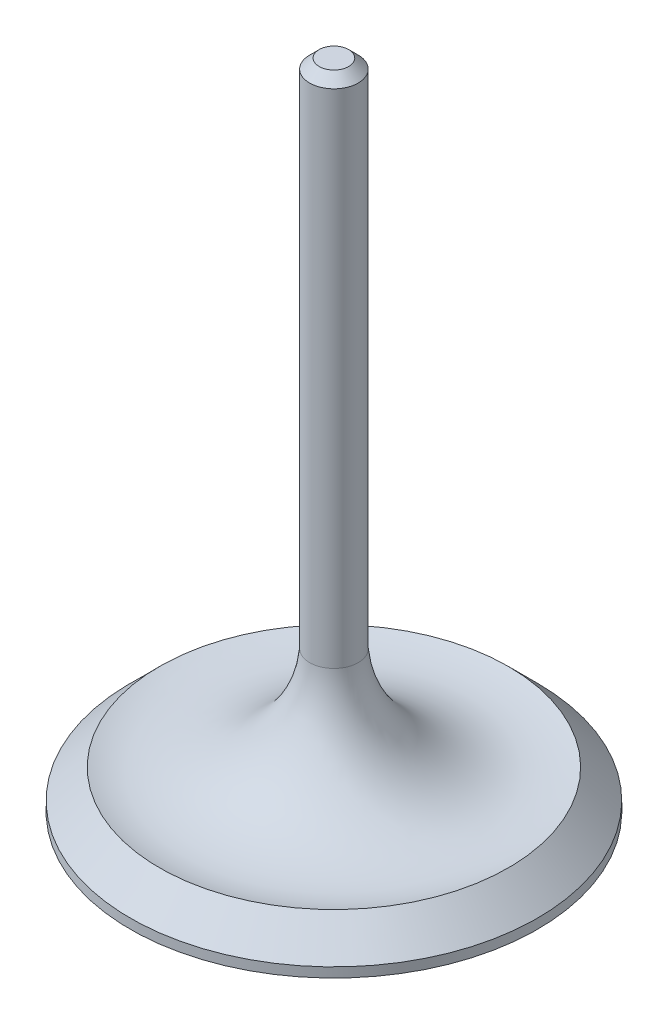
SolidWorks part; units mm, degrees
ref_plane "Front Plane" through (0, 0, 0) normal (0, 0, 1) x (1, 0, 0)
ref_plane "Top Plane" through (0, 0, 0) normal (0, 1, 0) x (1, 0, 0)
ref_plane "Right Plane" through (0, 0, 0) normal (1, 0, 0) x (0, 0, -1)
sketch "Sketch1" plane through (0, 0, 0) normal (1, 0, 0) x (0, 0, -1)
  line L0 (0, 0) -> (0, 85.55)
  line L1 (0, 85.55) -> (3.18, 85.55)
  line L2 (3.18, 85.55) -> (3.18, 18.522)
  line L3 (22.86, 5.08) -> (26.67, 1.27)
  line L4 (26.67, 1.27) -> (26.67, 0)
  line L5 (26.67, 0) -> (0, 0)
  arc A0 (3.18, 18.522) -> (22.86, 5.08) centre (18.3875, 19.6594) ccw
  dimension "D7" = 15.25
  dimension "D1" = 85.55
  dimension "D2" = 26.67
  dimension "D3" = 3.18
  dimension "D4" = 1.27
  dimension "D5" = 3.81
  dimension "D6" = 45
revolve "Revolve1" add sketch "Sketch1" angle 360 about L0
chamfer "Chamfer1" distance 1.25 angle 45 1 edges at (0, 85.55, -3.18)
scale "Scale1" scale about centroid uniform scaling yes scale factor 0.51948
